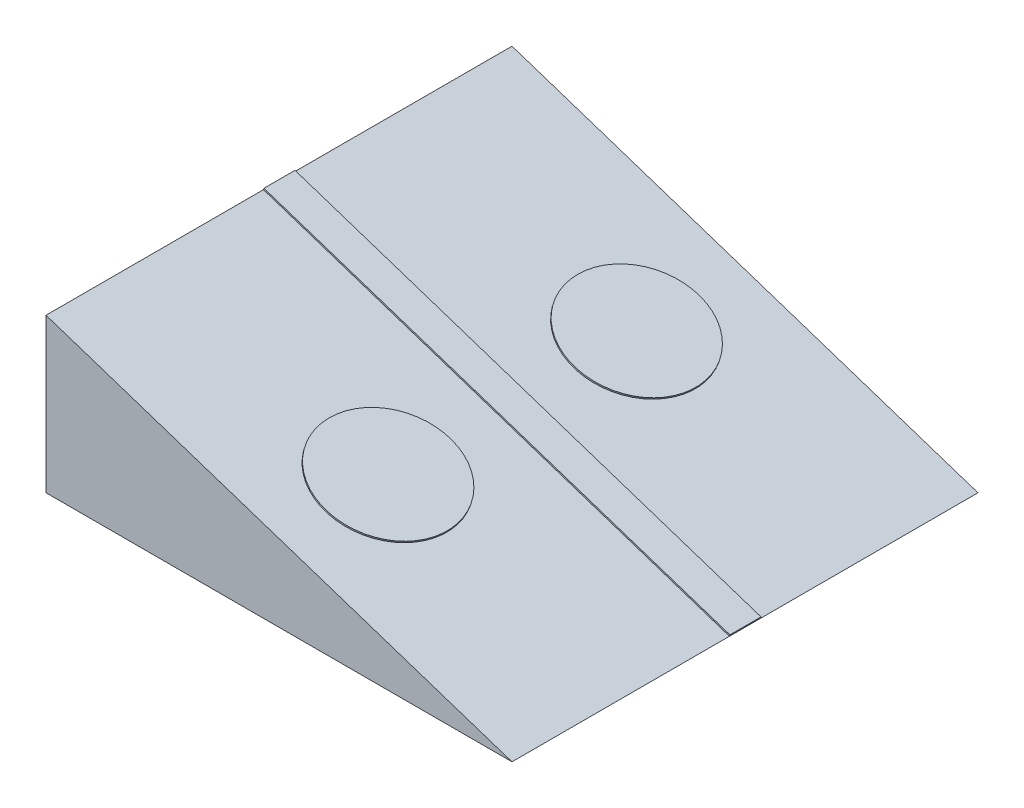
SolidWorks part; units mm, degrees
ref_plane "Спереди" through (0, 0, 0) normal (0, 0, 1) x (1, 0, 0)
ref_plane "Сверху" through (0, 0, 0) normal (0, 1, 0) x (1, 0, 0)
ref_plane "Справа" through (0, 0, 0) normal (1, 0, 0) x (0, 0, -1)
sketch "Эскиз1" plane through (0, 0, 0) normal (0, 0, 1) x (1, 0, 0)
  line L0 (0, 0) -> (300, 0)
  line L1 (0, 0) -> (0, 99)
  line L2 (0, 99) -> (300, 0)
  dimension "D1" = 300
  dimension "D2" = 99
extrude "Бобышка-Вытянуть1" add sketch "Эскиз1" against normal blind 300
sketch "Эскиз3" plane through (29.4616, 89.2777, 0) normal (0.3134, 0.9496, 0) x (0.9496, -0.3134, 0)
  line L0 (-31.0244, 300) -> (284.8886, 0)
  line L1 (284.8886, 300) -> (-31.0244, 0)
  line L3 (-31.0244, 140) -> (284.8886, 140)
  line L4 (-31.0244, 0) -> (284.8886, 0)
  line L5 (284.8886, 0) -> (284.8886, 300)
  line L6 (284.8886, 300) -> (-31.0244, 300)
  line L7 (-31.0244, 300) -> (-31.0244, 0)
  line L8 (-31.0244, 0) -> (284.8886, 0)
  line L9 (284.8886, 0) -> (284.8886, 300)
  line L10 (284.8886, 300) -> (-31.0244, 300)
  line L11 (-31.0244, 300) -> (-31.0244, 0)
  line L12 (-31.0244, 140) -> (-31.0244, 160)
  line L13 (-31.0244, 160) -> (284.8886, 160)
  line L14 (284.8886, 140) -> (284.8886, 160)
  line L15 (-31.0244, 140) -> (284.8886, 160) construction
  line L16 (-31.0244, 160) -> (284.8886, 140) construction
  point P2 (126.9321, 150)
  dimension "D2" = 20
  dimension "D1" = 0
extrude "Бобышка-Вытянуть2" add sketch "Эскиз3" along normal blind 1 contours L13 L11 L3 L1 L0 | L3 L14 L13 L12 region at (72.5287, 75.0655, -150)
sketch "Эскиз5" plane through (29.4616, 89.2777, 0) normal (0.3134, 0.9496, 0) x (0.9496, -0.3134, 0)
  line L0 (284.8886, 0) -> (284.8886, 140) construction
  line L1 (284.8886, 140) -> (-31.0244, 140) construction
  line L2 (-31.0244, 140) -> (-31.0244, 0) construction
  line L3 (-31.0244, 0) -> (284.8886, 0) construction
  line L8 (284.8886, 0) -> (284.8886, 140)
  line L9 (284.8886, 140) -> (-31.0244, 140)
  line L10 (-31.0244, 140) -> (-31.0244, 0)
  line L11 (-31.0244, 0) -> (284.8886, 0)
  line L18 (-31.0244, 140) -> (284.8886, 0) construction
  line L19 (284.8886, 140) -> (-31.0244, 0) construction
  circle A1 centre (126.9321, 70) radius 40
extrude "Бобышка-Вытянуть3" add sketch "Эскиз5" along normal blind 1 contours L19 A1 L18 | L18 A1 L19 | L19 A1 L18 | L18 A1 L19 region at (150, 49.5, -70)
sketch "Эскиз6" plane through (29.4616, 89.2777, 0) normal (0.3134, 0.9496, 0) x (0.9496, -0.3134, 0)
  line L0 (-31.0244, 300) -> (284.8886, 160) construction
  line L1 (284.8886, 300) -> (-31.0244, 160) construction
  line L4 (-31.0244, 160) -> (284.8886, 160)
  line L5 (284.8886, 160) -> (284.8886, 300)
  line L6 (284.8886, 300) -> (-31.0244, 300)
  line L7 (-31.0244, 300) -> (-31.0244, 160)
  line L8 (-31.0244, 160) -> (284.8886, 160) construction
  line L9 (284.8886, 160) -> (284.8886, 300) construction
  line L10 (284.8886, 300) -> (-31.0244, 300) construction
  line L11 (-31.0244, 300) -> (-31.0244, 160) construction
  circle A0 centre (126.9321, 230) radius 40
  dimension "D2" = 80
  dimension "D1" = 0
extrude "Бобышка-Вытянуть4" add sketch "Эскиз6" along normal blind 1
ref_plane "Середина" through (0, 0, -150) normal (0, 0, 1) x (1, 0, 0)
